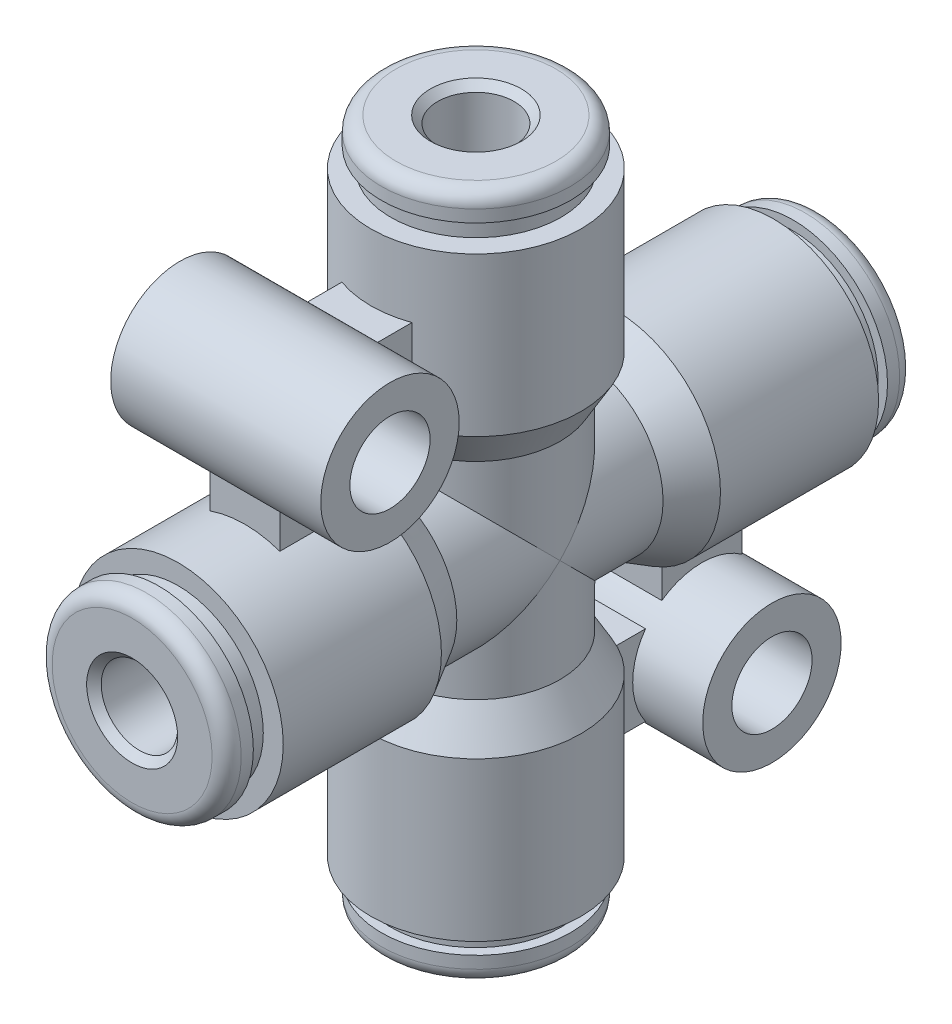
SolidWorks part; units mm, degrees
ref_plane "Front Plane" through (0, 0, 0) normal (0, 0, 1) x (1, 0, 0)
ref_plane "Top Plane" through (0, 0, 0) normal (0, 1, 0) x (1, 0, 0)
ref_plane "Right Plane" through (0, 0, 0) normal (1, 0, 0) x (0, 0, -1)
sketch "Sketch1" plane through (0, 0, 0) normal (1, 0, 0) x (0, 0, -1)
  line L0 (16.603, 4.95) -> (17.238, 4.95)
  line L1 (7.3053, 5.5) -> (15.587, 5.5)
  line L2 (0, 4.4) -> (0, 1.238)
  line L3 (7.7143, 2) -> (17.619, 2)
  line L4 (18, 4.188) -> (18, 2.381)
  line L5 (0, 0) -> (0, 18) construction
  line L6 (15.587, 5.5) -> (15.587, 4.455)
  line L7 (15.587, 4.455) -> (16.603, 4.455)
  line L8 (16.603, 4.95) -> (16.603, 4.455)
  line L9 (-5.5, 18) -> (5.5, 18) construction
  line L10 (0, 0) -> (18, 0) construction
  line L11 (7.7143, 2) -> (7.7143, 1.238)
  line L12 (17.619, 2) -> (18, 2.381)
  line L13 (0, 0) -> (0, 1.238) construction
  line L14 (0, 4.4) -> (5.4, 4.4)
  line L15 (5.4, 4.4) -> (7.3053, 5.5)
  line L16 (7.7143, 1.238) -> (0, 1.238)
  line L17 (10, 10) -> (-10, -10) construction
  line L18 (10, 10) -> (-10, 10) construction
  line L19 (10, 10) -> (10, -10) construction
  line L20 (10, -10) -> (-10, -10) construction
  line L21 (-10, 10) -> (-10, -10) construction
  line L22 (0, 0) -> (-18, 0) construction
  arc A0 (17.238, 4.95) -> (18, 4.188) centre (17.238, 4.188) cw
  circle A1 centre (10, -10) radius 2.1 construction
  circle A2 centre (-10, 10) radius 2.1 construction
  point P1 (18, 2)
  point P20 (18, 4.95)
  dimension "D4" = 0.762
  dimension "T" = 4.2
  dimension "D1" = 1.397
  dimension "H" = 36
  dimension "tube od" = 4
  dimension "D2" = 1.016
  dimension "D3" = 8.91
  dimension "D5" = 12.6
  dimension "G" = 11
  dimension "D6" = 9.9
  dimension "D8" = 11
  dimension "D9" = 30
  dimension "D10" = 8.8
  dimension "D11" = 0.762
  dimension "D" = 10.2857
  dimension "N" = 20
revolve "Revolve1" add sketch "Sketch1" angle 360 about L10
ref_axis "Axis1" through (-6.05, 0, 0) along (1, 0, 0)
pattern_circular "CirPattern1" count 4 over 360 about axis through (-6.05, 0, 0) along (1, 0, 0) of bodies 118 123
combine bodies "Combine1" operation type add bodies to combine 118 124 130 131
sketch "Sketch3" plane through (0, 0, 0) normal (1, 0, 0) x (0, 0, -1)
  line L0 (18, 2.381) -> (17.619, 2)
  line L1 (17.619, 2) -> (7.7143, 2)
  line L2 (7.7143, 2) -> (7.7143, 1.238)
  line L3 (7.7143, 1.238) -> (0, 1.238)
  line L4 (0, 1.238) -> (0, 0)
  line L5 (0, 0) -> (18, 0)
  line L6 (18, 0) -> (18, 2.381)
revolve "Cut-Revolve1" cut sketch "Sketch3" angle 360 about L5
pattern_circular "CirPattern2" count 4 over 360 about axis through (-6.05, 0, 0) along (1, 0, 0) of "Cut-Revolve1"
sketch "Sketch4" plane through (0, 0, 0) normal (1, 0, 0) x (0, 0, -1)
  circle A0 centre (-10, 10) radius 2.1 construction
  circle A1 centre (10, -10) radius 2.1 construction
  circle A2 centre (-10, 10) radius 2.1
  circle A3 centre (10, -10) radius 2.1
  circle A4 centre (-10, 10) radius 3.624
  circle A5 centre (10, -10) radius 3.624
  dimension "D1" = 1.524
extrude "Boss-Extrude1" add sketch "Sketch4" along normal mid plane 11 separate body
sketch "Sketch5" plane through (0, 0, 0) normal (1, 0, 0) x (0, 0, -1)
  line L0 (10, -12.1) -> (2, -12.1)
  line L1 (-2, 17.619) -> (-2, 7.7143) construction
  line L2 (2, -12.1) -> (2, -7.9)
  line L4 (2, -7.9) -> (7.9, -7.9)
  line L5 (2, -17.619) -> (2, -7.7143) construction
  line L7 (12.1, -10) -> (12.1, -2)
  line L8 (7.9, -7.9) -> (7.9, -2)
  line L9 (7.9, -2) -> (12.1, -2)
  line L10 (-10, 12.1) -> (-2, 12.1)
  line L11 (7.7143, -2) -> (17.619, -2) construction
  line L12 (-2, 12.1) -> (-2, 7.9)
  line L13 (-2, 7.9) -> (-7.9, 7.9)
  line L14 (-12.1, 10) -> (-12.1, 2)
  line L15 (-7.9, 7.9) -> (-7.9, 2)
  line L16 (-7.9, 2) -> (-12.1, 2)
  line L17 (-7.7143, 2) -> (-17.619, 2) construction
  circle A0 centre (-10, 10) radius 2.1 construction
  circle A1 centre (10, -10) radius 2.1 construction
  arc A2 (-12.1, 10) -> (-10, 12.1) centre (-10, 10) ccw
  arc A3 (12.1, -10) -> (10, -12.1) centre (10, -10) ccw
extrude "Boss-Extrude2" add sketch "Sketch5" along normal mid plane 3.6667
equation "\"D6@Sketch1\" = \"G@Sketch1\"*.9"
equation "\"D3@Sketch1\" = \"D6@Sketch1\"*.9"
equation "\"D10@Sketch1\" = \"G@Sketch1\"*.8"
equation "\"D5@Sketch1\" = \"H@Sketch1\"*.35"
equation "\"D8@Sketch1\" = \"G@Sketch1\""
equation "\"D1@Boss-Extrude1\" = \"G@Sketch1\""
equation "\"D1@Boss-Extrude2\" = \"G@Sketch1\" / 3"
